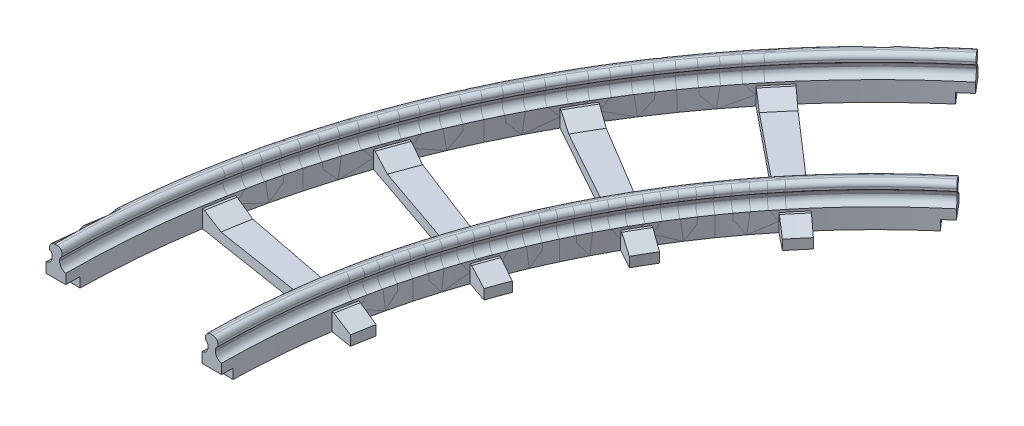
SolidWorks part; units mm, degrees
other "标注1"
sketch "草图3" plane through (-22.25, 4, -10) normal (-0.231, 0.6469, -0.7268) x (-0.9696, -0.2151, 0.1167)
ref_plane "前视基准面" through (0, 0, 0) normal (0, 0, 1) x (1, 0, 0)
ref_plane "上视基准面" through (0, 0, 0) normal (0, 1, 0) x (1, 0, 0)
ref_plane "右视基准面" through (0, 0, 0) normal (1, 0, 0) x (0, 0, -1)
other "Configuration Table"
sketch "草图4" plane through (0, 0, 0) normal (0, 0, 1) x (1, 0, 0)
  line L0 (0, 0) -> (31.5, 0) construction
  line L1 (0.75, -1.5) -> (1.25, -1.5)
  line L3 (0, 0) -> (1.25, 0)
  line L4 (1.25, -1.5) -> (1.25, 0)
  line L5 (0, 0) -> (-1.25, 0)
  line L10 (0.75, -1.5) -> (0.75, -4)
  line L11 (-0.75, -1.5) -> (-1.25, -1.5)
  line L12 (0.75, -4) -> (2, -4)
  line L14 (0, -8) -> (2, -8)
  line L15 (2, -4) -> (2, -8)
  line L16 (-1.25, 0) -> (-1.25, -1.5)
  line L20 (-0.75, -1.5) -> (-0.75, -4)
  line L21 (-0.75, -4) -> (-2, -4)
  line L23 (0, -8) -> (-2, -8)
  line L24 (-2, -4) -> (-2, -8)
  line L25 (31.5, 0) -> (32.75, 0)
  line L26 (30.25, 0) -> (31.5, 0)
  line L27 (30.25, 0) -> (30.25, -1.5)
  line L28 (30.25, -1.5) -> (30.75, -1.5)
  line L31 (30.75, -1.5) -> (30.75, -4)
  line L34 (29.5, -4) -> (30.75, -4)
  line L35 (29.5, -4) -> (29.5, -8)
  line L36 (29.5, -8) -> (31.5, -8)
  line L39 (32.25, -1.5) -> (32.75, -1.5)
  line L40 (32.75, 0) -> (32.75, -1.5)
  line L42 (32.25, -1.5) -> (32.25, -4)
  line L45 (32.25, -4) -> (33.5, -4)
  line L47 (31.5, -8) -> (33.5, -8)
  line L48 (33.5, -4) -> (33.5, -8)
  point P0 (0, 0)
  point P2 (15.75, 0)
  dimension "D1" = 1.25
  dimension "D4" = 2.5
sketch "草图6" plane through (0, 0, 0) normal (0, 0, 1) x (1, 0, 0)
  line L0 (165.75, 3.8535) -> (165.75, -12.2756)
  dimension "D1" = 150
revolve "旋转1" add sketch "草图4" angle 10 about L0
fillet "圆角1" radius 1.5 2 edges at (1.3779, -4, -14.3807) (-0.1164, -4, -14.5114)
fillet "圆角2" radius 1.5 2 edges at (31.2637, -4, -11.766) (32.758, -4, -11.6353)
fillet "圆角3" radius 1 4 edges at (33.2561, 0, -11.5917) (30.7656, 0, -11.8096) (31.2637, -1.5, -11.766) (32.758, -1.5, -11.6353)
fillet "圆角4" radius 1 4 edges at (1.876, 0, -14.3371) (-0.1164, -1.5, -14.5114) (1.3779, -1.5, -14.3807) (-0.6145, 0, -14.555)
sketch "草图7" plane through (0, 0, 0) normal (0, 0, 1) x (1, 0, 0)
  line L1 (-2, -8) -> (2, -8)
  line L2 (-2, -8) -> (-2, -6)
  line L3 (-2, -6) -> (2, -6)
  line L4 (2, -8) -> (2, -6)
  line L5 (33.5, -8) -> (33.5, -4) construction
  line L6 (29.5, -8) -> (33.5, -8)
  line L7 (29.5, -8) -> (29.5, -6)
  line L8 (29.5, -6) -> (33.5, -6)
  line L9 (33.5, -8) -> (33.5, -6)
  line L10 (2, -8) -> (2, -4) construction
  dimension "D1" = 2
sketch "草图9" plane through (0, 0, 0) normal (0, 1, 0) x (1, 0, 0)
  line L0 (29.5, 0) -> (2, 0)
  line L1 (-2, 0) -> (2, 0) construction
  line L2 (4.4877, 28.4349) -> (31.5699, 23.6596)
  line L3 (18.0288, 26.0472) -> (15.75, 0)
  arc A0 (4.4877, 28.4349) -> (2, 0) centre (165.75, 0) ccw construction
  arc A1 (31.5699, 23.6596) -> (29.5, 0) centre (165.75, 0) ccw construction
  point P20 (165.75, 0)
  dimension "D1" = 10
  dimension "D2" = 26.1467
revolve "切除-旋转1" cut sketch "草图7" angle 1 about L0
sketch "草图10" plane through (0, -6, 0) normal (0, -1, 0) x (1, 0, 0)
  line L0 (-1.9936, -1.4639) -> (2.0062, -1.429) construction
  line L2 (2.0062, -1.429) -> (29.5052, -1.189) construction
  line L3 (29.5052, -1.189) -> (33.505, -1.1541) construction
  circle A1 centre (0.0063, -1.4464) radius 0.4
  circle A2 centre (31.5051, -1.1715) radius 0.4
  arc A3 (-2, 0) -> (-1.9745, -2.9276) centre (165.75, 0) ccw construction
  arc A4 (2, 0) -> (2.0249, -2.8578) centre (165.75, 0) ccw construction
  arc A5 (29.5, 0) -> (29.5208, -2.3779) centre (165.75, 0) ccw construction
  arc A6 (33.5, 0) -> (33.5201, -2.3081) centre (165.75, 0) ccw construction
  dimension "D1" = 0.8
extrude "切除-拉伸1" cut sketch "草图10" against normal blind 2
sketch "草图11" plane through (4.998, 0, -28.3449) normal (0.1736, 0, -0.9848) x (-0.9848, 0, -0.1736)
  line L0 (-26.9819, -4.5) -> (-26.4819, -4.5)
  line L1 (-26.9819, -4) -> (-26.9819, -8) construction
  line L2 (-26.4819, -4.5) -> (-22.4819, -6)
  line L3 (-22.4819, -6) -> (-3.9819, -6)
  line L4 (-3.9819, -6) -> (0.0181, -4.5)
  line L5 (0.0181, -4.5) -> (0.5181, -4.5)
  line L6 (0.5181, -8) -> (0.5181, -4) construction
  line L7 (0.5181, -4.5) -> (4.5181, -4.5)
  line L8 (4.5181, -4) -> (4.5181, -8) construction
  line L9 (4.5181, -4.5) -> (5.0181, -4.5)
  line L10 (5.0181, -4.5) -> (9.0181, -6)
  line L11 (9.0181, -6) -> (9.0181, -8)
  line L13 (-35.4819, -8) -> (-35.4819, -6)
  line L14 (-35.4819, -6) -> (-31.4819, -4.5)
  line L15 (-31.4819, -4.5) -> (-30.9819, -4.5)
  line L16 (-30.9819, -8) -> (-30.9819, -4) construction
  line L17 (-30.9819, -4.5) -> (-26.9819, -4.5)
  line L19 (-35.4819, -8) -> (-30.9819, -8)
  line L20 (-30.9819, -8) -> (-26.9819, -8)
  line L21 (-26.9819, -8) -> (0.5181, -8)
  line L22 (0.5181, -8) -> (4.5181, -8)
  line L23 (4.5181, -8) -> (9.0181, -8)
  dimension "D1" = 0.5
  dimension "D2" = 4.5
  dimension "D3" = 3.5
  dimension "D4" = 2
revolve "旋转2" add sketch "草图11" angle 1 about L0
mirror "镜向1"
pattern_circular "阵列(圆周)1" count 4 every 10 about axis through (165.75, 0, 0) along (0, 1, 0) of bodies 229
